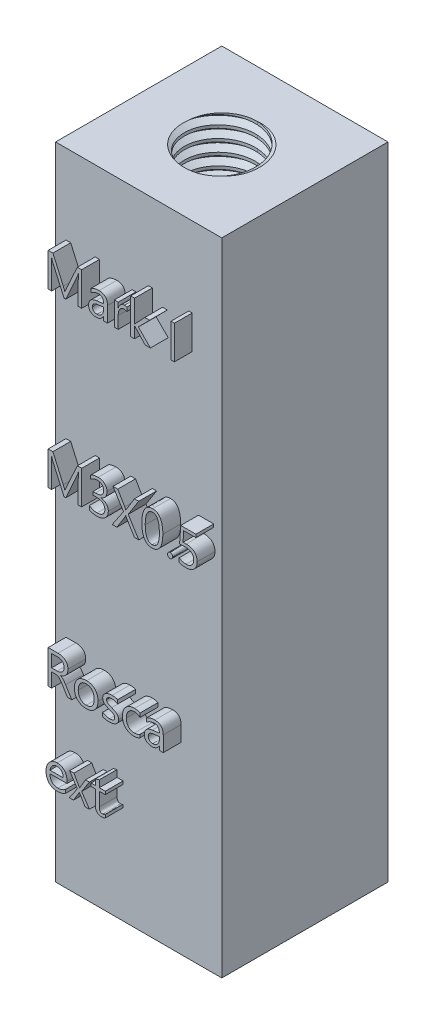
SolidWorks part; units mm, degrees
ref_plane "Alzado" through (0, 0, 0) normal (0, 0, 1) x (1, 0, 0)
ref_plane "Planta" through (0, 0, 0) normal (0, 1, 0) x (1, 0, 0)
ref_plane "Vista lateral" through (0, 0, 0) normal (1, 0, 0) x (0, 0, -1)
sketch "Croquis1" plane through (0, 0, 0) normal (0, 1, 0) x (1, 0, 0)
  line L1 (-3.5, 3.5) -> (3.5, 3.5)
  line L2 (-3.5, 3.5) -> (-3.5, -3.5)
  line L3 (-3.5, -3.5) -> (3.5, -3.5)
  line L4 (3.5, 3.5) -> (3.5, -3.5)
  line L5 (-3.5, 3.5) -> (3.5, -3.5) construction
  line L6 (-3.5, -3.5) -> (3.5, 3.5) construction
  circle A0 centre (0, 0) radius 1.5
  point P0 (0, 0)
  dimension "D1" = 3
  dimension "7" = 7
extrude "Saliente-Extruir1" add sketch "Croquis1" along normal blind 27
sketch "Croquis2" plane through (0, 0, 3.5) normal (0, 0, 1) x (1, 0, 0)
  text T0 "Mark I\r\n \r\nM3X0.5\r\n\r\nRosca\r\next" font "@Adobe Heiti Std R" height in points 5
split line "Línea de partición1"
extrude "Saliente-Extruir2" add sketch "Croquis2<2>" along normal blind 0.75
sketch "Croquis2<2>" plane through (0, 0, 3.5) normal (0, 0, 1) x (1, 0, 0) same geometry as "Croquis2"
thread "Rosca1" pitch 0.5 method cut profile "Perfil de rosca1" start angle 0, offset 1, length 25, pitch 0.5, diameter 3
ref_plane "Plano1" through (-1.5, 28, 0) normal (0, 0, 1) x (-1, 0, 0)
sketch "Perfil de rosca1" plane through (-1.5, 28, 0) normal (0, 0, 1) x (-1, 0, 0)
  line L0 (0, 0) -> (0, 0.5) construction
  line L1 (0, 0) -> (0.2706, 0.1562)
  line L2 (0.2706, 0.1562) -> (0.2706, 0.2187)
  line L3 (0.2706, 0.2187) -> (0, 0.375)
  line L4 (0.2706, 0.1875) -> (0, 0.1875) construction
  line L11 (0, 0) -> (0, 0.375)
  point P2 (0, 0)
  dimension "Pitch" = 0.5
  dimension "Profile_Angle" = 60
  dimension "Profile_Land" = 0.0625
  dimension "Profile_Height" = 0.2706
